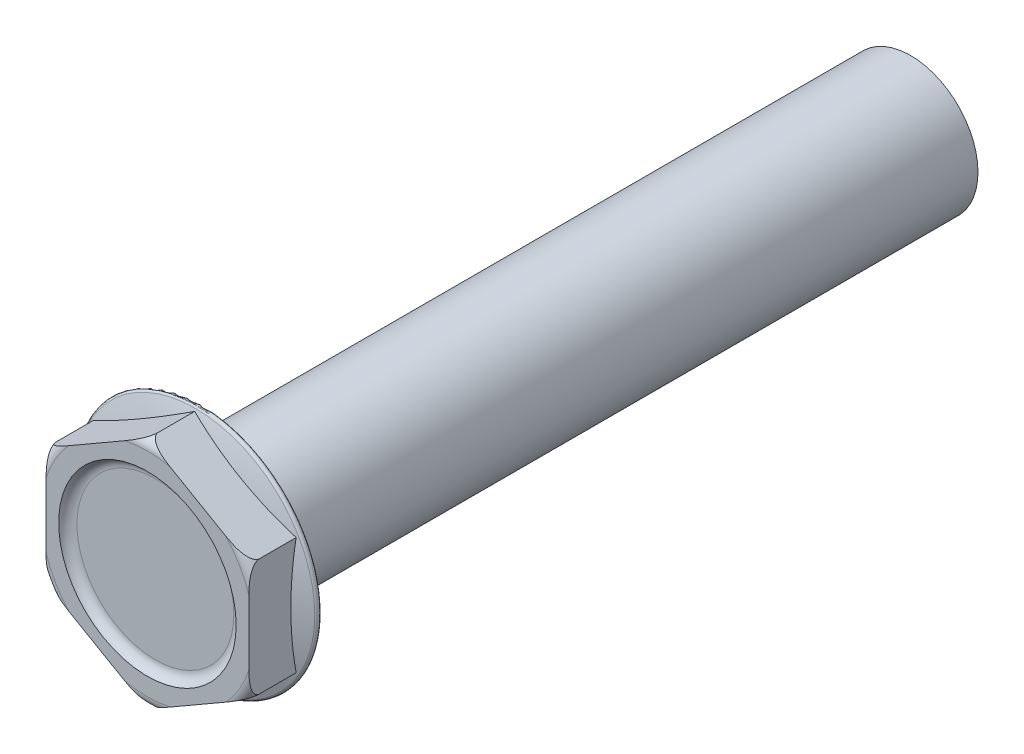
SolidWorks part; units mm, degrees
note: '?' marks a value the reader was unsure of.
extrude "Shank" add sketch "Shank Sketch" against normal blind 133.35
sketch "Shank Sketch" plane through (0, 0, 0) normal (0, 0, 1) x (1, 0, 0)
  line L0 (50, 0) -> (-50, 0) construction
  line L1 (0, -50) -> (0, 50) construction
  circle A0 centre (0, 0) radius 12.7
  dimension "Shank diameter" = 25.4
extrude "Head" add sketch "Head Sketch" along normal blind 10
sketch "Head Sketch" plane through (0, 0, 0) normal (0, 0, 1) x (1, 0, 0)
  line L0 (0, 21.997) -> (19.05, 10.9985)
  line L1 (19.05, 10.9985) -> (19.05, -10.9985)
  line L2 (19.05, -10.9985) -> (0, -21.997)
  line L3 (0, -21.997) -> (-19.05, -10.9985)
  line L4 (-19.05, -10.9985) -> (-19.05, 10.9985)
  line L5 (-19.05, 10.9985) -> (0, 21.997)
  line L6 (19.05, 10.9985) -> (-19.05, -10.9985) construction
  line L7 (0, 21.997) -> (0, -21.997) construction
  line L8 (-19.05, 10.9985) -> (19.05, -10.9985) construction
  point P0 (0, 0)
  dimension "D1" = 60
  dimension "D2" = 60
  dimension "Width across flats" = 38.1
ref_plane "Plane1" through (0, 0, 0) normal (0, 0, 1) x (1, 0, 0)
ref_plane "Plane2" through (0, 0, 0) normal (0, 1, 0) x (-1, 0, 0)
ref_plane "Plane3" through (0, 0, 0) normal (1, 0, 0) x (0, 0, -1)
other "Configuration Table"
sketch "Sketch3" plane through (0, 0, 0) normal (0, 1, 0) x (-1, 0, 0)
  line L0 (0, 0) -> (0, 10) construction
  line L1 (0, -133.35) -> (0, 0) construction
  line L4 (-22.225, 0) -> (0, 0)
  line L5 (0, 0) -> (0, 5)
  arc A0 (0, 5) -> (-22.3993, 0.9686) centre (0, -59.2438) ccw
  arc A1 (-22.225, 0) -> (-22.3993, 0.9686) centre (-22.225, 0.5) cw
  dimension "D1" = 0.5
  dimension "D2" = 44.45
  dimension "D3" = 5
revolve "Flange" add sketch "Sketch3" angle 360 about L0
ref_axis "Axis1" through (0, 0, -183.35) along (0, 0, 1)?
sketch "Sketch5" plane through (0, 0, 0) normal (1, 0, 0) x (0, 0, -1)
  line L0 (-10, -19.997) -> (-10, -21.997)
  line L1 (-10, -21.997) -> (-8, -21.997)
  line L2 (-10, -21.997) -> (-1.1168, -21.997) construction
  line L3 (-10, -21.997) -> (-10, -10.9985) construction
  line L5 (-15.0856, 0) -> (-8.1394, 0) construction
  line L6 (50, 0) -> (-50, 0) construction
  arc A0 (-10, -19.997) -> (-8, -21.997) centre (-8, -19.997) ccw
  dimension "D1" = 2
revolve "Head Trim" cut sketch "Sketch5" angle 360 about L5
sketch "Sketch6" plane through (0, 0, 10) normal (0, 0, 1) x (1, 0, 0)
  circle A3 centre (0, 0) radius 16.6687
  dimension "D1" = 33.3375
extrude "Head Cut" cut sketch "Sketch6" against normal blind 1.5
fillet "Fillet1" radius 2 1 edges at (16.6687, 0, 8.5)
fillet "Fillet2" radius 0.5 1 edges at (12.7, 0, 0)
sketch "Thread End" plane through (0, 0, 0) normal (1, 0, 0) x (0, 0, -1)
  line L0 (6.35, 12.7) -> (6.35, 12.65)
  line L1 (133.35, 12.7) -> (0.5, 12.7) construction
  line L2 (6.35, 12.65) -> (133.35, 12.65)
  line L3 (133.35, 12.7) -> (6.35, 12.7)
  line L4 (21.5519, 0) -> (27.4271, 0) construction
  line L5 (133.35, 0) -> (0.5, 0) construction
  line L6 (133.35, -12.7) -> (133.35, 12.7) construction
  line L7 (133.35, 12.65) -> (133.35, 12.7)
  dimension "D1" = 0.05
  dimension "Length of thread" = 127
revolve "Thread Cut" cut sketch "Thread End" angle 360 about L4
cosmetic thread "Cosmetic Thread2" parameters "D2"=11
equation "\"D1@Sketch6\" = \"Width across flats@Head Sketch\"*7/8"
